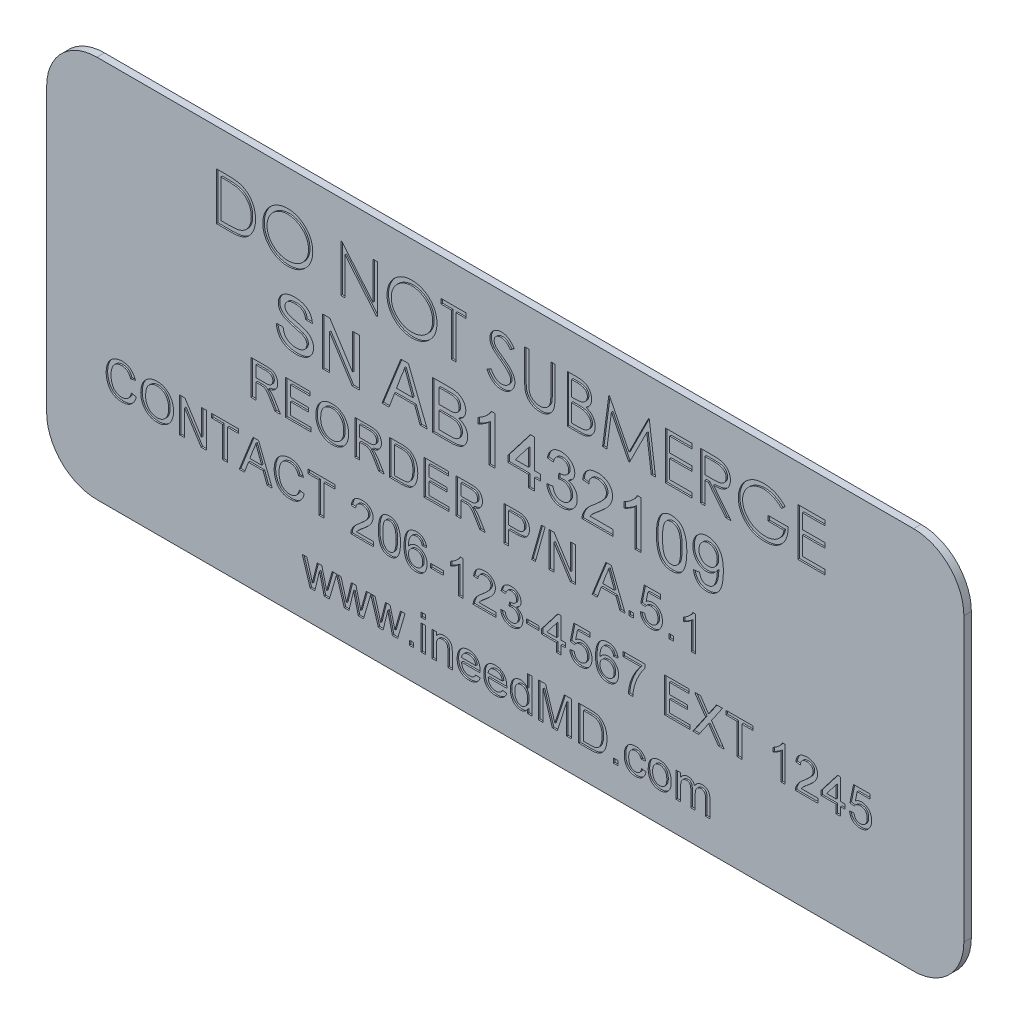
SolidWorks part; units mm, degrees
material "ABS PC"
ref_plane "CL Y" through (0, 0, 0) normal (0, 0, 1) x (1, 0, 0)
ref_plane "Bottom" through (0, 0, 0) normal (0, 1, 0) x (1, 0, 0)
ref_plane "CL X" through (0, 0, 0) normal (1, 0, 0) x (0, 0, -1)
sketch "Sketch1" plane through (0, 0, 0) normal (0, 0, 1) x (1, 0, 0)
  line L1 (0, -50) -> (0, 50) construction
  line L2 (-27.3, 12.81) -> (27.3, 12.81)
  line L3 (-30.66, 9.45) -> (-30.66, -9.45)
  line L4 (-27.3, -12.81) -> (27.3, -12.81)
  line L5 (30.66, 9.45) -> (30.66, -9.45)
  line L6 (50, 0) -> (-50, 0) construction
  arc A0 (30.66, -9.45) -> (27.3, -12.81) centre (27.3, -9.45) cw
  arc A1 (-27.3, -12.81) -> (-30.66, -9.45) centre (-27.3, -9.45) cw
  arc A2 (30.66, 9.45) -> (27.3, 12.81) centre (27.3, 9.45) ccw
  arc A3 (-27.3, 12.81) -> (-30.66, 9.45) centre (-27.3, 9.45) ccw
  point P0 (0, 12.81)
  point P7 (30.66, 0)
  point P12 (30.66, -12.81)
  point P17 (30.66, 12.81)
  point P20 (-30.66, 12.81)
  dimension "D3" = 3.36
  dimension "D1" = 61.32
  dimension "D2" = 25.62
extrude "Boss-Extrude1" add sketch "Sketch1" along normal blind 0.5
sketch "Sketch2" plane through (0, 0, 0.5) normal (0, 0, 1) x (1, 0, 0)
  line L0 (-15.5009, 2.3121) -> (22.8953, 2.3121) construction
  line L1 (-26.8299, -1.734) -> (22.8953, -1.734) construction
  line L2 (-13.5588, -10.7972) -> (22.8953, -10.7972) construction
  line L3 (-19.7088, 7.1673) -> (22.0465, 7.1673) construction
  text T0 "SN AB1432109" font "Arial" height 3.175
  text T1 "DO NOT SUBMERGE"
  text T2 "REORDER P/N A.5.1\r\nCONTACT 206-123-4567 EXT 1245" font "Arial" height in points 9
  text T3 "www.ineedMD.com" font "Arial" height in points 9
extrude "Cut-Extrude1" cut sketch "Sketch2" against normal blind 0.1
